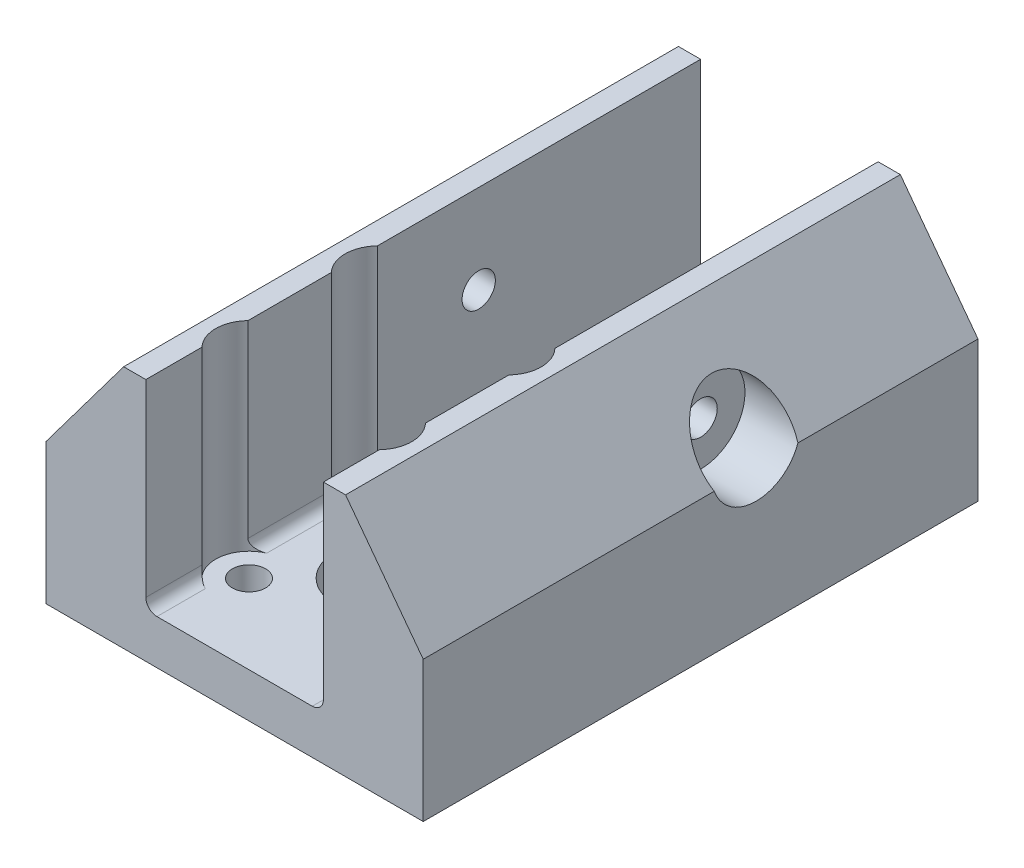
SolidWorks part; units mm, degrees
ref_plane "Front Plane" through (0, 0, 0) normal (0, 0, 1) x (1, 0, 0)
ref_plane "Top Plane" through (0, 0, 0) normal (0, 1, 0) x (1, 0, 0)
ref_plane "Right Plane" through (0, 0, 0) normal (1, 0, 0) x (0, 0, -1)
sketch "Sketch1" plane through (0, 0, 0) normal (0, 0, 1) x (1, 0, 0)
  line L1 (0, 0) -> (16, 0)
  line L2 (0, 0) -> (0, 16)
  line L3 (0, 16) -> (16, 16)
  line L4 (16, 0) -> (16, 16)
  line L5 (-2, 18) -> (18, 18)
  line L6 (-2, 18) -> (-2, -2)
  line L7 (-2, -2) -> (18, -2)
  line L8 (18, 18) -> (18, -2)
  dimension "D1" = 16
  dimension "D2" = 16
  dimension "D3" = 20
  dimension "D4" = 20
  dimension "D5" = 2
  dimension "D6" = 2
extrude "Boss-Extrude1" add sketch "Sketch1" along normal blind 50
sketch "Sketch2" plane through (0, 18, 0) normal (0, 1, 0) x (1, 0, 0)
  line L1 (0, 0) -> (16, 0)
  line L2 (0, 0) -> (0, -50)
  line L3 (0, -50) -> (16, -50)
  line L4 (16, 0) -> (16, -50)
  line L5 (18, -50) -> (18, 0) construction
  dimension "D1" = 2
  dimension "D2" = 50
extrude "Cut-Extrude1" cut sketch "Sketch2" against normal blind 13 contours L2 L3 L4 L1
sketch "Sketch4" plane through (0, -2, 0) normal (0, -1, 0) x (1, 0, 0)
  line L0 (-2, 50) -> (-2, 0) construction
  line L1 (-17, 50) -> (33, 50)
  line L2 (-17, 50) -> (-17, 0)
  line L3 (-17, 0) -> (33, 0)
  line L4 (33, 50) -> (33, 0)
  line L5 (18, 50) -> (18, 0) construction
  line L7 (-2, 50) -> (18, 50) construction
  dimension "D1" = 50
  dimension "D2" = 15
  dimension "D3" = 15
extrude "Boss-Extrude2" add sketch "Sketch4" along normal blind 2
sketch "Sketch5" plane through (0, 0, 0) normal (0, 0, -1) x (-1, 0, 0)
  line L0 (-18, 18) -> (-33, -2)
  line L1 (-33, -2) -> (-18, -2)
  line L2 (-18, -2) -> (-33, -2) construction
  line L3 (-18, -2) -> (-18, 18) construction
  line L4 (-18, -2) -> (-18, 18)
  line L5 (2, 18) -> (17, -2)
  line L6 (17, -2) -> (2, -2)
  line L7 (2, -2) -> (2, 18)
extrude "Boss-Extrude3" add sketch "Sketch5" against normal blind 50
sketch "Sketch6" plane through (0, -4, 0) normal (0, -1, 0) x (1, 0, 0)
  line L0 (-17, 0) -> (33, 0) construction
  line L1 (8, 0) -> (8, 50) construction
  line L2 (33, 50) -> (-17, 50) construction
  circle A1 centre (8, 37) radius 4
  dimension "D1" = 13
  dimension "D3" = 8
extrude "Cut-Extrude2" cut sketch "Sketch6" against normal blind 4 contours A1
sketch "Sketch7" plane through (0, -4, 0) normal (0, -1, 0) x (1, 0, 0)
  line L0 (8, 50) -> (8, 0) construction
  line L1 (33, 50) -> (-17, 50) construction
  line L2 (-17, 0) -> (33, 0) construction
  line L3 (8, 37.0385) -> (20.9615, 50) construction
  line L4 (8, 37.0385) -> (13.8336, 31.2048) construction
  line L5 (8, 37.0385) -> (2.1664, 31.2048) construction
  line L6 (8, 37.0385) -> (2.1664, 42.8721) construction
  circle A0 centre (8, 37.0385) radius 8.25 construction
  circle A1 centre (13.8336, 42.8721) radius 1.5
  circle A2 centre (13.8336, 31.2048) radius 1.5
  circle A3 centre (2.1664, 31.2048) radius 1.5
  circle A4 centre (2.1664, 42.8721) radius 1.5
  dimension "D1" = 16.5
  dimension "D3" = 3
  dimension "D8" = 3
  dimension "D9" = 3
  dimension "D10" = 3
  dimension "D2" = 12.9615
  dimension "D4" = 45
  dimension "D5" = 90
  dimension "D6" = 90
  dimension "D7" = 90
extrude "Cut-Extrude3" cut sketch "Sketch7" against normal through all contours A3 | A4 | A1 | A2 region at (13.8336, -4, 42.8721) region at (2.1664, -4, 31.2048) region at (2.1664, -4, 42.8721)
sketch "Sketch8" plane through (0, 0, 0) normal (0, 1, 0) x (1, 0, 0)
  line L0 (0, 0) -> (16, 0) construction
  line L1 (8, -37) -> (8, 0) construction
  circle A0 centre (8, -12) radius 2
  dimension "D2" = 4
  dimension "D1" = 12
extrude "Cut-Extrude4" cut sketch "Sketch8" against normal through all
fillet "Fillet1" radius 1 2 edges at (16, 0, 25) (0, 0, 25)
sketch "Sketch11" plane through (0, 0, 0) normal (1, 0, 0) x (0, 0, -1)
  line L1 (0, 18) -> (-50, 18) construction
  line L2 (0, 18) -> (0, -2) construction
  circle A1 centre (-20, 10) radius 1.5
  dimension "D1" = 20
  dimension "D2" = 3
  dimension "D6" = 8
extrude "Cut-Extrude5" cut sketch "Sketch11" against normal through all both and the other way through all
sketch "Sketch12" plane through (0, 0, 50) normal (0, 0, 1) x (1, 0, 0)
  line L0 (-17, -2) -> (-2, 18) construction
  line L1 (-9, 8.6667) -> (-17, 8.6667)
  line L2 (-9, 8.6667) -> (-9, -4)
  line L3 (-9, -4) -> (-17, -4)
  line L4 (-17, 8.6667) -> (-17, -4)
  line L5 (18, 18) -> (33, -2) construction
  line L6 (33, -4) -> (25, -4)
  line L7 (33, -4) -> (33, 8.6667)
  line L8 (33, 8.6667) -> (25, 8.6667)
  line L9 (25, -4) -> (25, 8.6667)
  point P12 (0, 0)
  dimension "D1" = 8
  dimension "D2" = 8
extrude "Cut-Extrude6" cut sketch "Sketch12" against normal through all
sketch "Sketch13" plane through (0, 0, 0) normal (0, 1, 0) x (1, 0, 0)
  line L0 (2.1664, -31.2048) -> (13.8336, -31.2048) construction
  circle A0 centre (8, -37) radius 8.2228 construction
  circle A1 centre (2.1664, -31.2048) radius 3
  circle A2 centre (13.8336, -31.2048) radius 3
  circle A3 centre (13.8336, -42.8721) radius 3
  circle A4 centre (2.1664, -42.8721) radius 3
  point P15 (8, -37.0385)
  dimension "D1" = 6
  dimension "D2" = 4
extrude "Cut-Extrude7" cut sketch "Sketch13" along normal through all
sketch "Sketch15" plane through (25, 0, 0) normal (1, 0, 0) x (0, 0, -1)
  circle A0 centre (-20, 10) radius 4
  dimension "D1" = 8
extrude "Cut-Extrude8" cut sketch "Sketch15" against normal blind 5
sketch "Sketch16" plane through (-9, 0, 0) normal (-1, 0, 0) x (0, 0, 1)
  circle A1 centre (20, 10) radius 4
  dimension "D1" = 8
extrude "Cut-Extrude9" cut sketch "Sketch16" against normal blind 5
sketch "Sketch17" plane through (0, -4, 0) normal (0, -1, 0) x (1, 0, 0)
  circle A0 centre (8, 12) radius 3.9939
  dimension "D1" = 7.9877
extrude "Cut-Extrude10" cut sketch "Sketch17" against normal blind 2
